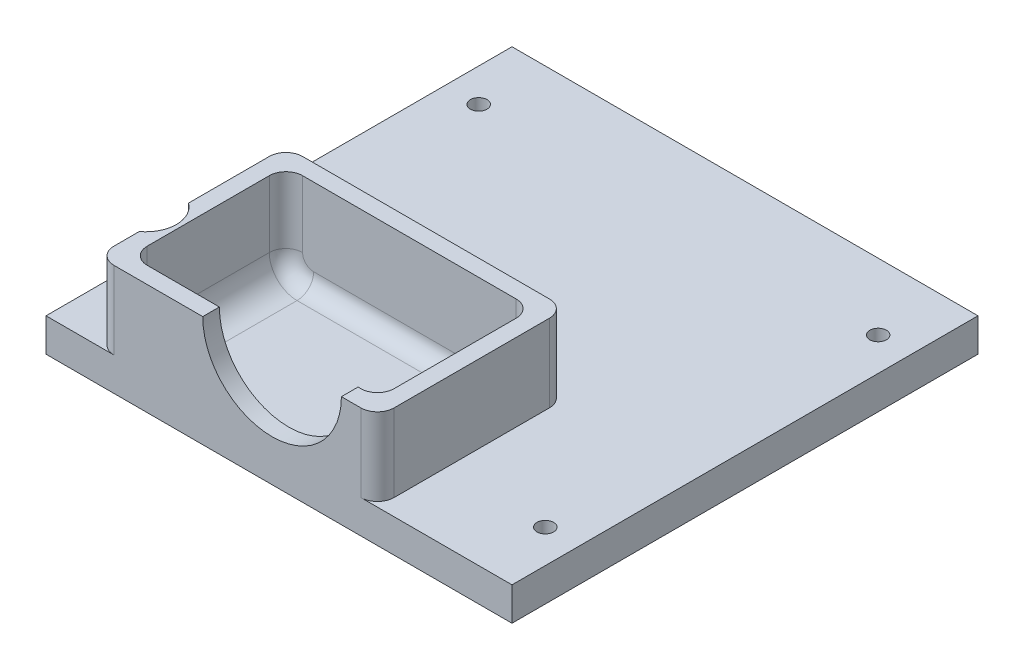
SolidWorks part; units mm, degrees
material "PVB"
ref_plane "Front Plane" through (0, 0, 0) normal (0, 0, 1) x (1, 0, 0)
ref_plane "Top Plane" through (0, 0, 0) normal (0, 1, 0) x (1, 0, 0)
ref_plane "Right Plane" through (0, 0, 0) normal (1, 0, 0) x (0, 0, -1)
sketch "Sketch1" plane through (0, 0, 0) normal (0, 1, 0) x (1, 0, 0)
  line L1 (0, 0) -> (84, 0)
  line L2 (0, 0) -> (0, 84)
  line L3 (0, 84) -> (84, 84)
  line L4 (84, 0) -> (84, 84)
  dimension "D1" = 84
  dimension "D2" = 84
extrude "Boss-Extrude1" add sketch "Sketch1" along normal blind 6
sketch "Sketch2" plane through (0, 6, 0) normal (0, 1, 0) x (1, 0, 0)
  line L0 (84, 84) -> (0, 84) construction
  line L1 (0, 84) -> (0, 0) construction
  line L2 (0, 0) -> (84, 0) construction
  line L3 (84, 0) -> (84, 84) construction
  circle A0 centre (6, 72) radius 1.5
  circle A1 centre (6, 12) radius 1.5
  circle A2 centre (78, 12) radius 1.5
  circle A3 centre (78, 72) radius 1.5
  dimension "D1" = 3
  dimension "D2" = 3
  dimension "D3" = 3
  dimension "D4" = 3
  dimension "D6" = 6
  dimension "D7" = 12
  dimension "D8" = 6
  dimension "D9" = 6
  dimension "D10" = 12
  dimension "D11" = 6
  dimension "D5" = 12
  dimension "D12" = 12
extrude "Cut-Extrude1" cut sketch "Sketch2" against normal through all
ref_plane "Plane1" through (0, 0, -42) normal (0, 0, 1) x (1, 0, 0)
sketch "Sketch4" plane through (0, 6, 0) normal (0, 1, 0) x (1, 0, 0)
  line L0 (3, 21) -> (3, 9)
  line L1 (3, 9) -> (13, 9)
  line L2 (13, 15) -> (8, 21)
  line L3 (3, 21) -> (8, 21)
  line L4 (8, 21) -> (13, 15)
  line L5 (13, 15) -> (13, 9)
  line L6 (0, 84) -> (0, 0) construction
  line L7 (0, 0) -> (84, 0) construction
  circle A0 centre (6, 12) radius 1.5
  circle A1 centre (6, 12) radius 1.5 construction
  dimension "D1" = 3
  dimension "D2" = 9
  dimension "D3" = 12
  dimension "D4" = 10
  dimension "D5" = 6
  dimension "D6" = 5
ref_plane "Plane2" through (42, 0, 0) normal (-1, 0, 0) x (0, 0, 1)
sketch "Sketch5" plane through (0, 6, 0) normal (0, 1, 0) x (1, 0, 0)
  line L0 (9.25, 34) -> (9.25, 0)
  line L1 (9.25, 34) -> (59.75, 34)
  line L2 (9.25, 0) -> (59.75, 0)
  line L3 (59.75, 34) -> (59.75, 0)
  line L4 (9.25, 34) -> (59.75, 0) construction
  line L5 (9.25, 0) -> (59.75, 34) construction
  line L6 (42, 3.3) -> (42, -3.3) construction
  line L12 (0, 0) -> (84, 0) construction
  point P1 (34.5, 17)
  dimension "D1" = 50.5
  dimension "D2" = 34
  dimension "D3" = 7.5
extrude "Boss-Extrude2" add sketch "Sketch5" along normal blind 22
sketch "Sketch6" plane through (0, 28, 0) normal (0, 1, 0) x (1, 0, 0)
  line L14 (56.75, 31) -> (12.25, 31)
  line L15 (12.25, 31) -> (12.25, 3)
  line L16 (12.25, 3) -> (56.75, 3)
  line L17 (56.75, 3) -> (56.75, 31)
  line L18 (56.75, 31) -> (12.25, 31)
  line L19 (12.25, 31) -> (12.25, 3)
  line L20 (12.25, 3) -> (56.75, 3)
  line L21 (56.75, 3) -> (56.75, 31)
  dimension "D1" = 3
extrude "Cut-Extrude5" cut sketch "Sketch6" against normal blind 25
fillet "Fillet1" radius 3 10 edges at (56.75, 15.5, -31) (12.25, 15.5, -31) (56.75, 15.5, -3) (12.25, 15.5, -3) (9.25, 17, -34) (59.75, 17, 0) (59.75, 17, -34) (9.25, 17, 0) (34.5, 3, -3) (34.5, 3, -31)
fillet "Fillet2" radius 5 6 edges at (13.1287, 3.8787, -3.8787) (13.1287, 3.8787, -30.1213) (55.8713, 3.8787, -30.1213) (55.8713, 3.8787, -3.8787) (56.75, 3, -17) (12.25, 3, -17)
sketch "Sketch8" plane through (0, 0, 0) normal (0, 0, 1) x (1, 0, 0)
  line L1 (0, 0) -> (84, 0) construction
  line L3 (59.75, 28) -> (59.75, 6) construction
  circle A0 centre (40.75, 20) radius 12.5
  dimension "D2" = 25
  dimension "D1" = 19
  dimension "D3" = 20
extrude "Cut-Extrude6" cut sketch "Sketch8" against normal blind 10
sketch "Sketch9" plane through (0, 0, 0) normal (0, 0, 1) x (1, 0, 0)
  line L0 (0, 0) -> (84, 0) construction
  line L1 (0, 28) -> (84, 28)
  line L2 (0, 28) -> (0, 20)
  line L3 (0, 20) -> (84, 20)
  line L4 (84, 28) -> (84, 20)
  line L5 (84, 6) -> (84, 0) construction
  line L6 (0, 6) -> (0, 0) construction
  line L7 (12.25, 28) -> (31.1453, 28) construction
  dimension "D1" = 20
extrude "Cut-Extrude7" cut sketch "Sketch9" against normal through all both and the other way through all
sketch "Sketch11" plane through (0, 0, 0) normal (0, -1, 0) x (1, 0, 0)
  line L0 (3, -9) -> (13, -9)
  line L1 (13, -9) -> (13, -15)
  line L2 (13, -15) -> (8, -21)
  line L3 (8, -21) -> (3, -21)
  line L4 (3, -21) -> (3, -9)
extrude "Cut-Extrude8" cut sketch "Sketch11" against normal blind 3
mirror "Mirror1" about plane through (0, 0, -42) normal (0, 0, 1) of "Cut-Extrude8" second plane through (42, 0, 0) second plane normal (-1, 0, 0)
sketch "Sketch13" plane through (0, 20, 0) normal (0, 1, 0) x (1, 0, 0)
  line L12 (53.25, 0) -> (56.75, 0)
  line L13 (59.75, 3) -> (59.75, 31)
  line L14 (56.75, 34) -> (12.25, 34)
  line L15 (9.25, 31) -> (9.25, 3)
  line L16 (12.25, 0) -> (28.25, 0)
  line L17 (28.25, 0) -> (28.25, 3)
  line L18 (28.25, 3) -> (15.25, 3)
  line L19 (12.25, 6) -> (12.25, 28)
  line L20 (15.25, 31) -> (53.75, 31)
  line L21 (56.75, 28) -> (56.75, 6)
  line L22 (53.75, 3) -> (53.25, 3)
  line L23 (53.25, 3) -> (53.25, 0)
  line L24 (53.25, 0) -> (56.75, 0)
  line L25 (59.75, 3) -> (59.75, 31)
  line L26 (56.75, 34) -> (12.25, 34)
  line L27 (9.25, 31) -> (9.25, 3)
  line L28 (12.25, 0) -> (28.25, 0)
  line L29 (28.25, 0) -> (28.25, 3)
  line L30 (28.25, 3) -> (15.25, 3)
  line L31 (12.25, 6) -> (12.25, 28)
  line L32 (15.25, 31) -> (53.75, 31)
  line L33 (56.75, 28) -> (56.75, 6)
  line L34 (53.75, 3) -> (53.25, 3)
  line L35 (53.25, 3) -> (53.25, 0)
  circle A0 centre (6, 12) radius 1.5 construction
  circle A1 centre (6, 12) radius 1.5
  circle A2 centre (6, 12) radius 5.5
  arc A8 (56.75, 0) -> (59.75, 3) centre (56.75, 3) ccw
  arc A9 (59.75, 31) -> (56.75, 34) centre (56.75, 31) ccw
  arc A10 (12.25, 34) -> (9.25, 31) centre (12.25, 31) ccw
  arc A11 (9.25, 3) -> (12.25, 0) centre (12.25, 3) ccw
  arc A12 (12.25, 6) -> (15.25, 3) centre (15.25, 6) ccw
  arc A13 (15.25, 31) -> (12.25, 28) centre (15.25, 28) ccw
  arc A14 (56.75, 28) -> (53.75, 31) centre (53.75, 28) ccw
  arc A15 (53.75, 3) -> (56.75, 6) centre (53.75, 6) ccw
  arc A16 (56.75, 0) -> (59.75, 3) centre (56.75, 3) ccw
  arc A17 (59.75, 31) -> (56.75, 34) centre (56.75, 31) ccw
  arc A18 (12.25, 34) -> (9.25, 31) centre (12.25, 31) ccw
  arc A19 (9.25, 3) -> (12.25, 0) centre (12.25, 3) ccw
  arc A20 (12.25, 6) -> (15.25, 3) centre (15.25, 6) ccw
  arc A21 (15.25, 31) -> (12.25, 28) centre (15.25, 28) ccw
  arc A22 (56.75, 28) -> (53.75, 31) centre (53.75, 28) ccw
  arc A23 (53.75, 3) -> (56.75, 6) centre (53.75, 6) ccw
  dimension "D2" = 11
  dimension "D1" = 0
extrude "Cut-Extrude9" cut sketch "Sketch13" against normal up to surface (14 mm away) contours L27 A2 L31 region at (10.1679, 20, -12) up to face at (6, 6, -70.5)
